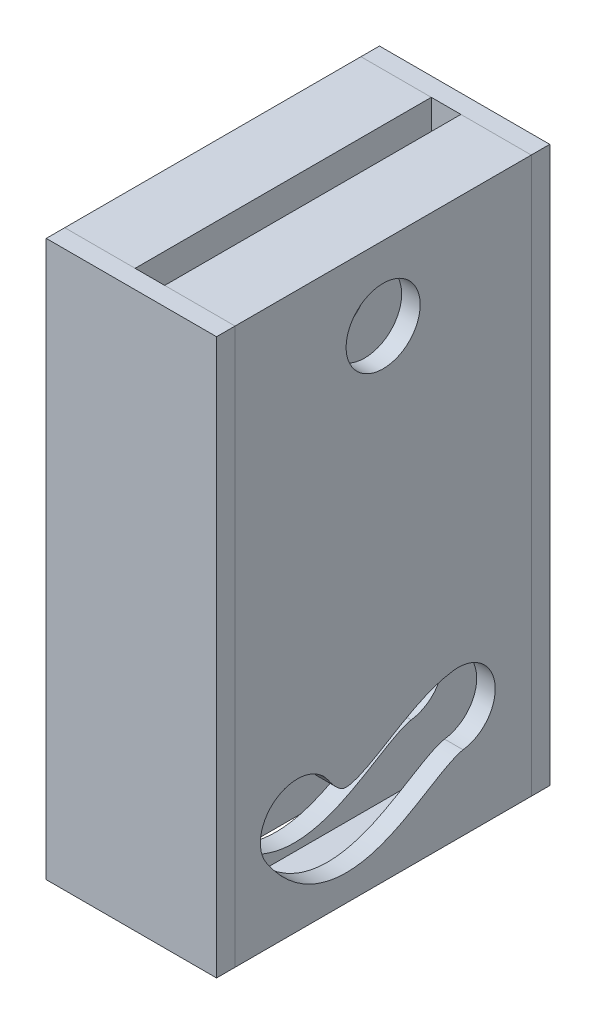
SolidWorks part; units mm, degrees
ref_plane "Front Plane" through (0, 0, 0) normal (0, 0, 1) x (1, 0, 0)
ref_plane "Top Plane" through (0, 0, 0) normal (0, 1, 0) x (1, 0, 0)
ref_plane "Right Plane" through (0, 0, 0) normal (1, 0, 0) x (0, 0, -1)
sketch "Sketch1" plane through (0, 0, 0) normal (0, 0, 1) x (1, 0, 0)
  line L0 (-4, 75) -> (-4, 35)
  line L8 (-4, -35) -> (-4, -75)
  line L9 (-4, -75) -> (-23, -75)
  line L10 (-23, -75) -> (-23, 75)
  line L11 (-23, 75) -> (-4, 75)
  line L12 (0, 171.0434) -> (0, -171.0434) construction
  line L13 (-4, 35) -> (4, 35)
  line L14 (-4, -35) -> (4, -35)
  line L15 (4, -35) -> (4, -75)
  line L16 (4, -75) -> (23, -75)
  line L17 (23, -75) -> (23, 75)
  line L18 (4, 75) -> (4, 35)
  line L19 (23, 75) -> (4, 75)
  line L20 (-18, 70) -> (-9, 70)
  line L21 (-9, 70) -> (-9, 30)
  line L22 (-9, 30) -> (9, 30)
  line L23 (9, 70) -> (9, 30)
  line L24 (18, 70) -> (9, 70)
  line L25 (18, -70) -> (18, 70)
  line L26 (9, -70) -> (18, -70)
  line L27 (9, -30) -> (9, -70)
  line L28 (-9, -30) -> (9, -30)
  line L29 (-9, -30) -> (-9, -70)
  line L30 (-9, -70) -> (-18, -70)
  line L31 (-18, -70) -> (-18, 70)
  line L32 (-71.2515, 55) -> (71.2515, 55) construction
  line L33 (-18, 0) -> (18, 0) construction
  line L34 (-23, 65) -> (23, 65) construction
  line L35 (-23, -65) -> (23, -65) construction
  line L36 (-71.2515, -55) -> (71.2515, -55) construction
  point P6 (0, -35)
  point P16 (0, 35)
  point P31 (0, 0)
  point P34 (0, 55)
  point P35 (-4, 55)
  point P36 (71.2515, 55)
  point P39 (-20, 0)
  dimension "D2" = 10
  dimension "D3" = 8
  dimension "D4" = 46
  dimension "D5" = 150
  dimension "D6" = 20
  dimension "D1" = 5
sketch "Sketch2" plane through (0, 0, 0) normal (1, 0, 0) x (0, 0, -1)
  line L0 (-40, 0) -> (40, 0) construction
  line L1 (-40, 0) -> (-45, 0) construction
  line L2 (40, 0) -> (45, 0) construction
  point P3 (0, 0)
  point P4 (0, 0)
  point P7 (40, 0)
  point P8 (0, 0)
  point P9 (0, 0)
  point P10 (0, 0)
  point P11 (0, 0)
  point P12 (0, 0)
  point P13 (0, 0)
  dimension "D1" = 80
  dimension "D2" = 5
extrude "Boss-Extrude1" add sketch "Sketch1" along normal up to vertex (40 mm away) and the other way up to vertex (40 mm away) up to point (0, 0, 40) other way up to point (0, 0, -40)
sketch "Sketch3" plane through (0, 0, 0) normal (0, 0, 1) x (1, 0, 0)
  line L1 (-23, -75) -> (23, -75)
  line L2 (-23, -75) -> (-23, 75)
  line L3 (-23, 75) -> (23, 75)
  line L4 (23, -75) -> (23, 75)
  line L5 (-23, -75) -> (23, 75) construction
  line L6 (-23, 75) -> (23, -75) construction
  point P0 (0, 0)
extrude "Boss-Extrude2" add sketch "Sketch3" along normal up to vertex (45 mm away) from vertex separate body up to point (0, 0, 45) starting at point (0, 0, 40)
extrude "Boss-Extrude3" add sketch "Sketch3<2>" against normal up to vertex (45 mm away) from vertex separate body up to point (0, 0, -45) starting at point (0, 0, -40)
sketch "Sketch3<2>" plane through (0, 0, 0) normal (0, 0, 1) x (1, 0, 0) same geometry as "Sketch3"
sketch "Sketch4" plane through (0, 0, 0) normal (1, 0, 0) x (0, 0, -1)
  line L0 (0, 171.0434) -> (0, -171.0434) construction
  circle A0 centre (0, 55) radius 10
  circle A1 centre (0, -55) radius 10 construction
  arc A2 (-31.4617, -54.9352) -> (-14.8827, -43.7487) centre (-23.1722, -49.342) cw
  arc A3 (21.5877, -54.9129) -> (18.9531, -35.0871) centre (20.2704, -45) ccw
  spline S0 degree 3 poles (-23.1722, -49.342) (-9.1837, -70.0737) (6.7542, -46.7961) (20.2704, -45) knots 0 0 0 0 1 1 1 1 construction
  spline S1 degree 1 poles (-31.4617, -54.9352) (21.5877, -54.9129) knots 0 0 1 1 construction
  spline S2 degree 3 poles (-31.4617, -54.9352) (-30.913, -55.7484) (-29.7473, -57.359) (-27.3068, -60.2469) (-23.9206, -63.3578) (-19.2822, -66.1168) (-14.2588, -67.686) (-9.2968, -68.0371) (-4.7395, -67.4454) (-0.6629, -66.254) (4.2173, -64.2022) (8.4538, -61.802) (12.2348, -59.5117) (14.8357, -57.9446) (17.1724, -56.627) (18.8426, -55.8121) (19.9554, -55.359) (20.6614, -55.1187) (21.1238, -54.997) (21.4202, -54.9377) (21.5283, -54.9208) (21.5877, -54.9129) knots 0 0 0 0 0.03125 0.0625 0.125 0.1875 0.25 0.3125 0.375 0.4375 0.5 0.625 0.6875 0.75 0.8125 0.875 0.90625 0.9375 0.96875 0.984375 1 1 1 1
  spline S3 degree 1 poles (-14.8827, -43.7487) (18.9531, -35.0871) knots 0 0 1 1 construction
  spline S4 degree 3 poles (-14.8827, -43.7487) (-14.732, -43.9721) (-14.4132, -44.428) (-13.827, -45.2053) (-13.1419, -46.0112) (-12.4318, -46.7144) (-11.6443, -47.3576) (-10.9805, -47.7182) (-10.5151, -47.8548) (-9.948, -47.9126) (-8.6179, -47.7812) (-5.7019, -46.7954) (-0.9385, -44.1508) (3.653, -41.2952) (7.7222, -38.9894) (11.0302, -37.353) (14.0932, -36.1732) (16.7705, -35.4494) (18.2306, -35.1832) (18.9531, -35.0871) knots 0 0 0 0 0.015625 0.03125 0.0625 0.09375 0.125 0.1875 0.25 0.3125 0.375 0.5 0.625 0.75 0.8125 0.875 0.9375 0.96875 1 1 1 1
  point P10 (0, -55)
  dimension "D1" = 20
  dimension "D2" = 10
  dimension "D3" = 10
extrude "Cut-Extrude1" cut sketch "Sketch4" against normal through all and the other way through all
